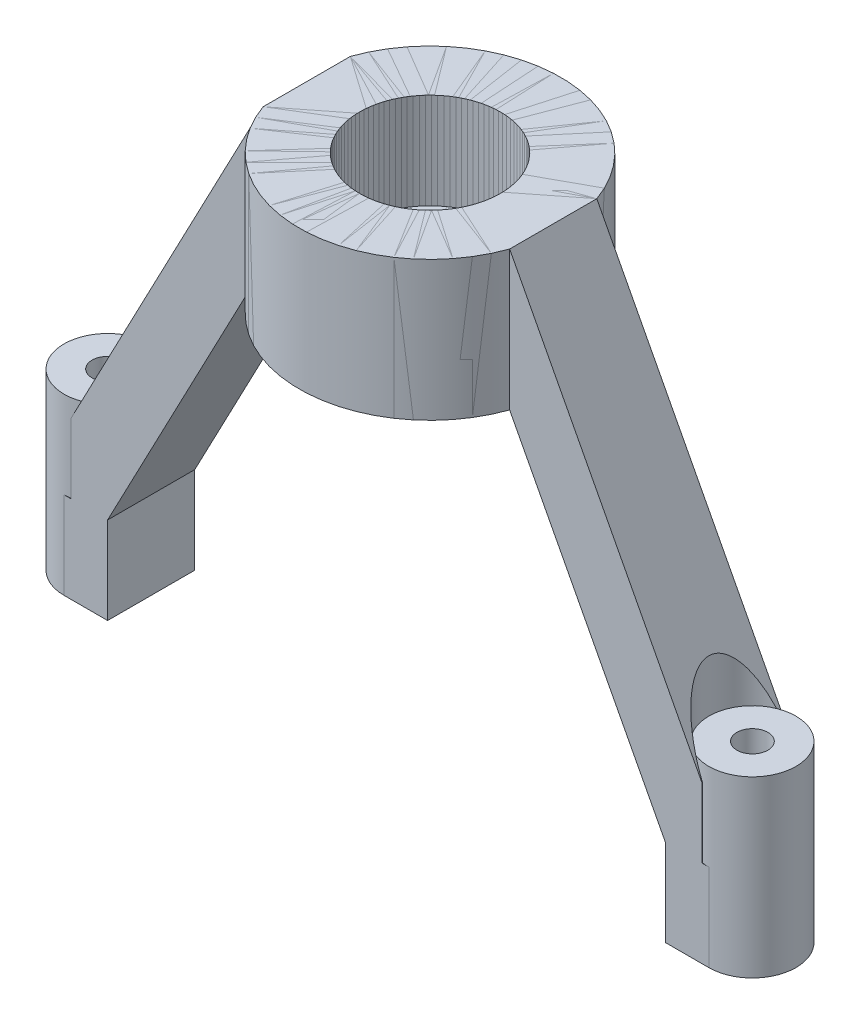
SolidWorks part; units mm, degrees
ref_plane "Front Plane" through (0, 0, 0) normal (0, 0, 1) x (1, 0, 0)
ref_plane "Top Plane" through (0, 0, 0) normal (0, 1, 0) x (1, 0, 0)
ref_plane "Right Plane" through (0, 0, 0) normal (1, 0, 0) x (0, 0, -1)
sketch "Sketch1" plane through (0, 0, 0) normal (0, 1, 0) x (1, 0, 0)
  line L2 (7.0711, 2.5) -> (7.0711, -2.5)
  line L4 (-26.3789, 0) -> (26.3789, 0) construction
  line L5 (-7.0711, 2.5) -> (-18.0711, 2.5) construction
  line L6 (7.0711, -2.5) -> (26.3789, -2.5) construction
  line L7 (0, 0) -> (0, 16.7972) construction
  line L11 (-7.0711, 2.5) -> (-7.0711, -2.5)
  arc A0 (-7.0711, -2.5) -> (7.0711, -2.5) centre (0, 0) ccw
  arc A1 (7.0711, 2.5) -> (-7.0711, 2.5) centre (0, 0) ccw
  circle A2 centre (-18.5, 0) radius 0.889
  circle A3 centre (0, 0) radius 1.875
  circle A8 centre (-18.5, 0) radius 2.5
  dimension "D3" = 15
  dimension "D5" = 3.75
extrude "Boss-Extrude1" add sketch "Sketch1" along normal blind 8 contours L2 A1 L11 A0 A3 region at (6.8649, 0, 0)
extrude "Boss-Extrude2" add sketch "Sketch1<3>" along normal blind 5 from offset 17 separate body contours A8 A2 region at (-20.9293, 0, 0) offset against normal yes
sketch "Sketch1<3>" plane through (0, 0, 0) normal (0, 1, 0) x (1, 0, 0) same geometry as "Sketch1"
sketch "Sketch3" plane through (0, 0, 0) normal (0, 0, 1) x (1, 0, 0)
  line L0 (-7.0711, 8) -> (-18.0983, -12.9949)
  line L1 (-18.0983, -12.9949) -> (-18.0983, -17)
  line L2 (-18.0983, -17) -> (-16, -17)
  line L3 (-16, -17) -> (-7.0711, 0)
  line L4 (-7.0711, 0) -> (-7.0711, 8)
sketch "Sketch4" plane through (0, 8, 0) normal (0, 1, 0) x (1, 0, 0)
  circle A0 centre (0, 0) radius 4.05
extrude "Cut-Extrude1" cut sketch "Sketch4" against normal blind 5.5
extrude "Boss-Extrude3" add sketch "Sketch3" along normal blind 2.5 and the other way blind 2.5
sketch "Sketch5" plane through (0, -12, 0) normal (0, 1, 0) x (1, 0, 0)
  circle A0 centre (-18.5, 0) radius 2.5
  circle A1 centre (-18.5, 0) radius 1.6841
  circle A4 centre (-18.5, 0) radius 2.5 construction
extrude "Cut-Extrude2" cut sketch "Sketch5" along normal through all contours A0
sketch "Sketch8" plane through (0, -17, 0) normal (0, -1, 0) x (1, 0, 0)
  line L0 (-18.5, -2.5) -> (-16, -2.5)
  line L1 (-16, -2.5) -> (-16, 2.5)
  line L2 (-16, 2.5) -> (-18.5, 2.5)
  arc A0 (-18.5, 2.5) -> (-18.5, -2.5) centre (-18.5, 0) ccw
  circle A2 centre (-18.5, 0) radius 0.889
extrude "Boss-Extrude4" add sketch "Sketch8" along normal blind 5
extrude "Cut-Extrude3" cut sketch "Sketch1<4>" against normal through all contours A2 region at (-18.5, 0, 0)
sketch "Sketch1<4>" plane through (0, 0, 0) normal (0, 1, 0) x (1, 0, 0) same geometry as "Sketch1"
pattern_circular "CirPattern5" count 2 over 360 about axis through (0, 8, 0) along (0, 1, 0) of bodies 116 113
